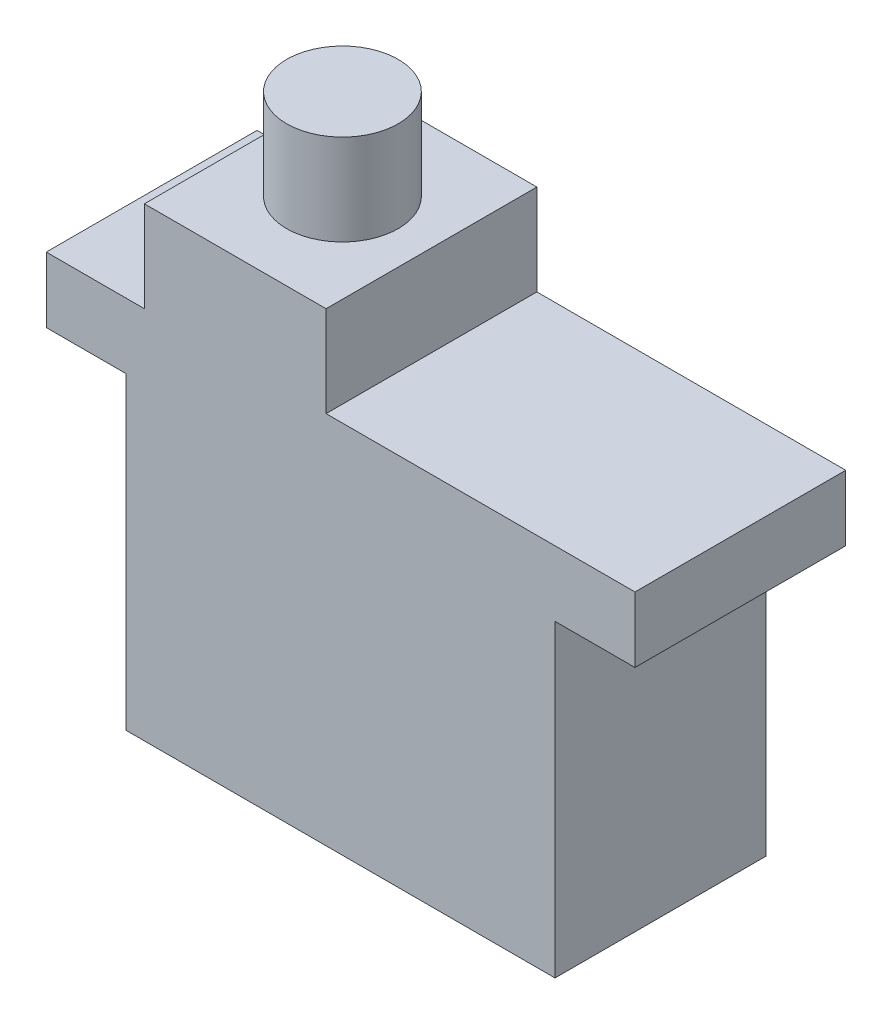
SolidWorks part; units mm, degrees
ref_plane "Front Plane" through (0, 0, 0) normal (0, 0, 1) x (1, 0, 0)
ref_plane "Top Plane" through (0, 0, 0) normal (0, 1, 0) x (1, 0, 0)
ref_plane "Right Plane" through (0, 0, 0) normal (1, 0, 0) x (0, 0, -1)
sketch "Sketch1" plane through (0, 0, 0) normal (0, 1, 0) x (1, 0, 0)
  line L1 (-11.8, -5.8) -> (11.8, -5.8)
  line L2 (-11.8, -5.8) -> (-11.8, 5.8)
  line L3 (-11.8, 5.8) -> (11.8, 5.8)
  line L4 (11.8, -5.8) -> (11.8, 5.8)
  line L5 (-11.8, -5.8) -> (11.8, 5.8) construction
  line L6 (-11.8, 5.8) -> (11.8, -5.8) construction
  point P0 (0, 0)
  dimension "D1" = 11.6
  dimension "D2" = 23.6
extrude "Boss-Extrude1" add sketch "Sketch1" along normal blind 17
sketch "Sketch2" plane through (0, 17, 0) normal (0, 1, 0) x (1, 0, 0)
  line L1 (-16.2, -5.8) -> (16.2, -5.8)
  line L2 (-16.2, -5.8) -> (-16.2, 5.8)
  line L3 (-16.2, 5.8) -> (16.2, 5.8)
  line L4 (16.2, -5.8) -> (16.2, 5.8)
  line L5 (-16.2, -5.8) -> (16.2, 5.8) construction
  line L6 (-16.2, 5.8) -> (16.2, -5.8) construction
  point P0 (0, 0)
  dimension "D1" = 11.6
  dimension "D2" = 32.4
extrude "Boss-Extrude2" add sketch "Sketch2" along normal blind 3.6
sketch "Sketch3" plane through (0, 20.6, 0) normal (0, 1, 0) x (1, 0, 0)
  line L0 (16.2, 5.8) -> (-16.2, 5.8) construction
  line L1 (-10.8, -5.8) -> (-0.8, -5.8)
  line L2 (-10.8, -5.8) -> (-10.8, 5.8)
  line L3 (-10.8, 5.8) -> (-0.8, 5.8)
  line L4 (-0.8, -5.8) -> (-0.8, 5.8)
  line L5 (-10.8, -5.8) -> (-0.8, 5.8) construction
  line L6 (-10.8, 5.8) -> (-0.8, -5.8) construction
  line L9 (-11.8, 5.8) -> (-11.8, -5.8) construction
  point P0 (-5.8, 0)
  dimension "D1" = 1
  dimension "D2" = 10
extrude "Boss-Extrude3" add sketch "Sketch3" along normal blind 5
sketch "Sketch4" plane through (0, 25.6, 0) normal (0, 1, 0) x (1, 0, 0)
  line L0 (-16.2, 5.8) -> (-16.2, -5.8) construction
  circle A0 centre (-5.7, 0) radius 3.0711
  dimension "D1" = 10.5
extrude "Boss-Extrude4" add sketch "Sketch4" along normal blind 5
